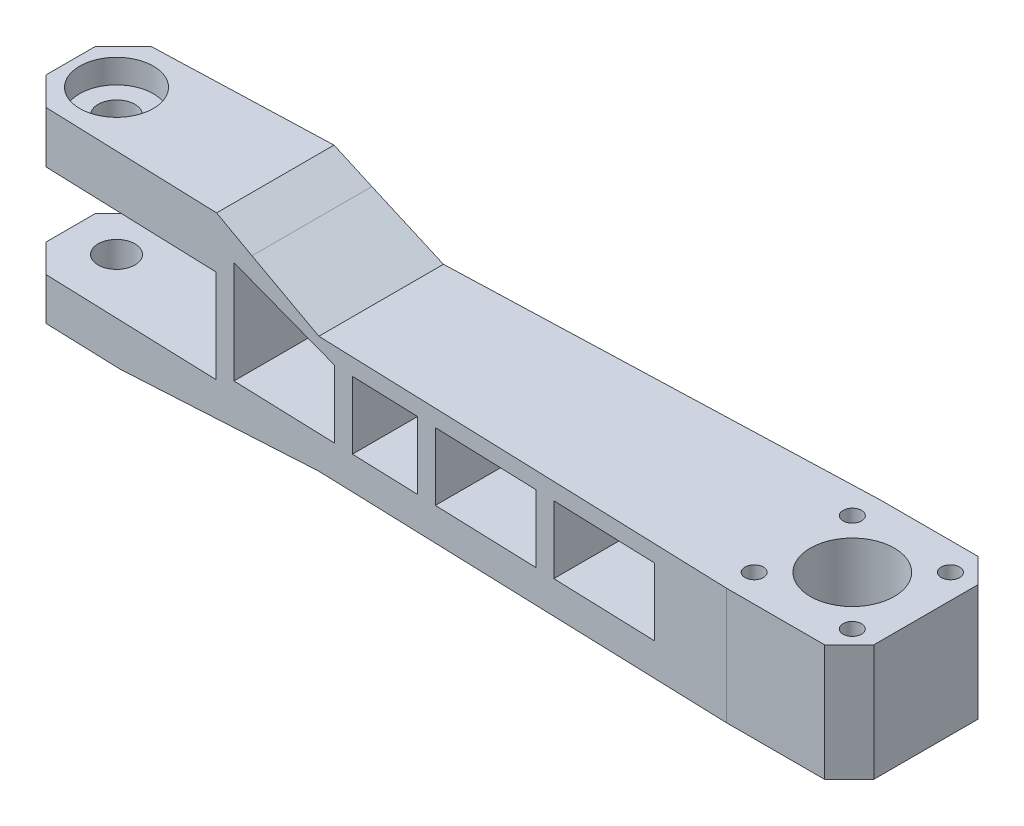
SolidWorks part; units mm, degrees
ref_plane "Front Plane" through (0, 0, 0) normal (0, 0, 1) x (1, 0, 0)
ref_plane "Top Plane" through (0, 0, 0) normal (0, 1, 0) x (1, 0, 0)
ref_plane "Right Plane" through (0, 0, 0) normal (1, 0, 0) x (0, 0, -1)
sketch "Sketch1" plane through (0, 0, 0) normal (0, 1, 0) x (1, 0, 0)
  line L0 (0, 0) -> (0, 47.3823) construction
  line L1 (0, 0) -> (-64.4031, 0) construction
  line L2 (0, 0) -> (79.7809, 0) construction
  line L3 (66.314, 14.6055) -> (66.314, -10.5011) construction
  line L4 (78.314, 8.5) -> (78.314, -8.5)
  line L5 (78.314, -8.5) -> (74.3118, -12.5022)
  line L6 (74.3118, -12.5022) -> (58.3118, -12.5022)
  line L7 (-61.186, 4) -> (-61.186, -4)
  line L8 (-61.186, -4) -> (-56.5898, -8.5962)
  line L9 (-56.5898, -8.5962) -> (58.3118, -12.5022)
  line L10 (78.314, 8.5) -> (74.3118, 12.5022)
  line L11 (74.3118, 12.5022) -> (58.3118, 12.5022)
  line L12 (-56.5898, 8.5962) -> (58.3118, 12.5022)
  line L13 (-61.186, 4) -> (-56.5898, 8.5962)
  circle A0 centre (-53.686, 0) radius 3
  circle A1 centre (66.314, 0) radius 6.85
  circle A2 centre (-53.686, 0) radius 6
  circle A3 centre (66.314, 0) radius 7.8
  circle A7 centre (58.314, 8) radius 1.5
  circle A8 centre (74.314, 8) radius 1.5
  circle A9 centre (58.314, -8) radius 1.5
  circle A10 centre (74.314, -8) radius 1.5
  point P23 (66.314, 0)
  point P29 (78.314, 0)
  point P33 (-61.186, 0)
  dimension "D1" = 120
  dimension "D2" = 12
  dimension "D3" = 6
  dimension "D4" = 13.7
  dimension "D5" = 15.6
  dimension "D6" = 8
  dimension "D7" = 8
  dimension "D9" = 12
  dimension "D10" = 8.5
  dimension "D11" = 135
  dimension "D12" = 5.66
  dimension "D13" = 16
  dimension "D14" = 135
  dimension "D15" = 7.5
  dimension "D16" = 4
  dimension "D17" = 135
  dimension "D18" = 6.5
extrude "Boss-Extrude1" add sketch "Sketch1" along normal blind 30.5 contours L13 L7 L8 L9 L6 L5 L4 L10 L11 L12 A7 A10 A9 A8 A3 A2 | A3 A1 | A2 A0 region at (12.0528, 0, 0) region at (-59.5163, 0, 0) region at (58.7346, 0, 0)
extrude "Cut-Extrude1" cut sketch "Sketch1<3>" against normal blind 3.9 from offset 30.5 contours A2
sketch "Sketch1<3>" plane through (0, 0, 0) normal (0, 1, 0) x (1, 0, 0) same geometry as "Sketch1"
extrude "Cut-Extrude2" cut sketch "Sketch1<4>" along normal mid plane 1.5 contours A3
sketch "Sketch1<4>" plane through (0, 0, 0) normal (0, 1, 0) x (1, 0, 0) same geometry as "Sketch1"
extrude "Cut-Extrude3" cut sketch "Sketch1<5>" against normal blind 1.5 from offset 30.5 contours A3
sketch "Sketch1<5>" plane through (0, 0, 0) normal (0, 1, 0) x (1, 0, 0) same geometry as "Sketch1"
sketch "Sketch3" plane through (0, 0, 0) normal (0, 0, 1) x (1, 0, 0)
  line L0 (-61.186, 15.25) -> (78.314, 15.25) construction
  line L1 (-61.186, 30.5) -> (-61.186, 0) construction
  line L2 (78.314, 30.5) -> (78.314, 0) construction
  line L3 (78.314, 30.5) -> (78.314, 3)
  line L4 (-61.186, 30.5) -> (-61.186, 22.1)
  line L5 (-61.186, 0) -> (-61.186, 6.9)
  line L7 (78.314, 3) -> (78.314, 22)
  line L8 (78.314, 22) -> (78.314, 3)
  line L9 (-61.186, 30.5) -> (-27.786, 30.5)
  line L10 (-56.5898, 30.5) -> (58.3118, 30.5) construction
  line L11 (-60.4805, 0) -> (-44.0805, 0)
  line L12 (-61.186, 0) -> (-56.5898, 0) construction
  line L13 (-56.5898, 0) -> (58.3118, 0) construction
  line L14 (-61.186, 22.1) -> (-27.8568, 22.1)
  line L15 (-27.8568, 22.1) -> (-27.8568, 6.9)
  line L16 (-27.8568, 6.9) -> (-61.186, 6.9)
  line L17 (-61.186, 22.1) -> (-61.186, 6.9)
  line L18 (78.314, 22) -> (-10.526, 22)
  line L19 (-21.8178, 27.5283) -> (-10.526, 22)
  line L20 (-27.786, 30.5) -> (-21.8178, 27.5283)
  line L21 (-44.0805, 0) -> (-10.526, 2.9356)
  line L22 (78.314, 3) -> (-10.526, 2.9356)
  line L23 (-27.786, 30.5) -> (39.4474, 56.9362)
  line L24 (39.4474, 56.9362) -> (78.314, 30.5)
  line L25 (-44.0805, 0) -> (9.3742, -19.7337)
  line L26 (9.3742, -19.7337) -> (78.314, 0)
  line L27 (78.314, 0) -> (78.314, 3)
  dimension "D4" = 19
  dimension "D1" = 8.4
  dimension "D2" = 6.9
  dimension "D3" = 8.5
  dimension "D5" = 33.4
  dimension "D6" = 16.4
  dimension "D7" = 175
  dimension "D8" = 153.53
  dimension "D9" = 88.84
  dimension "D10" = 88.84
extrude "Cut-Extrude4" cut sketch "Sketch3" against normal mid plane 50 contours L0 L17 L16 L15 | L17 L0 L15 L14 | L26 L27 L22 L21 L25 | L24 L23 L20 L19 L18 L3 region at (-44.5214, 18.675, 0) region at (16.7463, -4.9352, 0) region at (-44.5214, 11.075, 0) region at (29.7849, 34.5069, 0)
sketch "Sketch4" plane through (0, 0, 0) normal (0, 0, 1) x (1, 0, 0)
  line L0 (-27.8568, 8.276) -> (58.3118, 8.276) construction
  line L1 (-27.8568, 6.9) -> (-27.8568, 22.1) construction
  line L2 (58.3118, 22) -> (58.3118, 2.9855) construction
  line L3 (-27.8568, 19.276) -> (58.3118, 19.276) construction
  line L4 (-24.8568, 8.276) -> (-24.8568, 24.9915)
  line L5 (-24.8568, 24.9915) -> (-7.8568, 19.276)
  line L6 (-7.8568, 19.276) -> (-7.8568, 8.276)
  line L7 (-7.8568, 8.276) -> (-24.8568, 8.276)
  line L8 (-4.8568, 19.276) -> (6.1432, 19.276)
  line L9 (6.1432, 19.276) -> (6.1432, 8.276)
  line L10 (6.1432, 8.276) -> (-4.8568, 8.276)
  line L11 (-4.8568, 8.276) -> (-4.8568, 19.276)
  line L12 (10.4665, 19.276) -> (26.1432, 19.276)
  line L13 (26.1432, 19.276) -> (26.1432, 8.276)
  line L14 (26.1432, 8.276) -> (9.1432, 8.276)
  line L15 (9.1432, 8.276) -> (9.1432, 19.276)
  line L16 (9.1432, 19.276) -> (10.4665, 19.276)
  line L17 (29.1432, 19.276) -> (46.1432, 19.276)
  line L18 (46.1432, 19.276) -> (46.1432, 8.276)
  line L19 (46.1432, 8.276) -> (29.1432, 8.276)
  line L20 (29.1432, 8.276) -> (29.1432, 19.276)
  dimension "D1" = 11
  dimension "D2" = 11
  dimension "D3" = 17
  dimension "D4" = 11
  dimension "D5" = 17
  dimension "D6" = 17
  dimension "D7" = 3
  dimension "D8" = 3
  dimension "D9" = 3
  dimension "D10" = 3
extrude "Cut-Extrude5" cut sketch "Sketch4" against normal mid plane 50 contours L7 L6 L5 L4 | L11 L10 L9 L8 | L16 L15 L14 L13 L12 region at (-16.9411, 15.3031, 0) region at (0.6432, 13.776, 0) region at (17.6432, 13.776, 0)
extrude "Cut-Extrude6" cut sketch "Sketch4<3>" against normal blind 30 from offset 20 contours L20 L19 L18 L17 region at (37.6432, 13.776, 0)
sketch "Sketch4<3>" plane through (0, 0, 0) normal (0, 0, 1) x (1, 0, 0) same geometry as "Sketch4"
